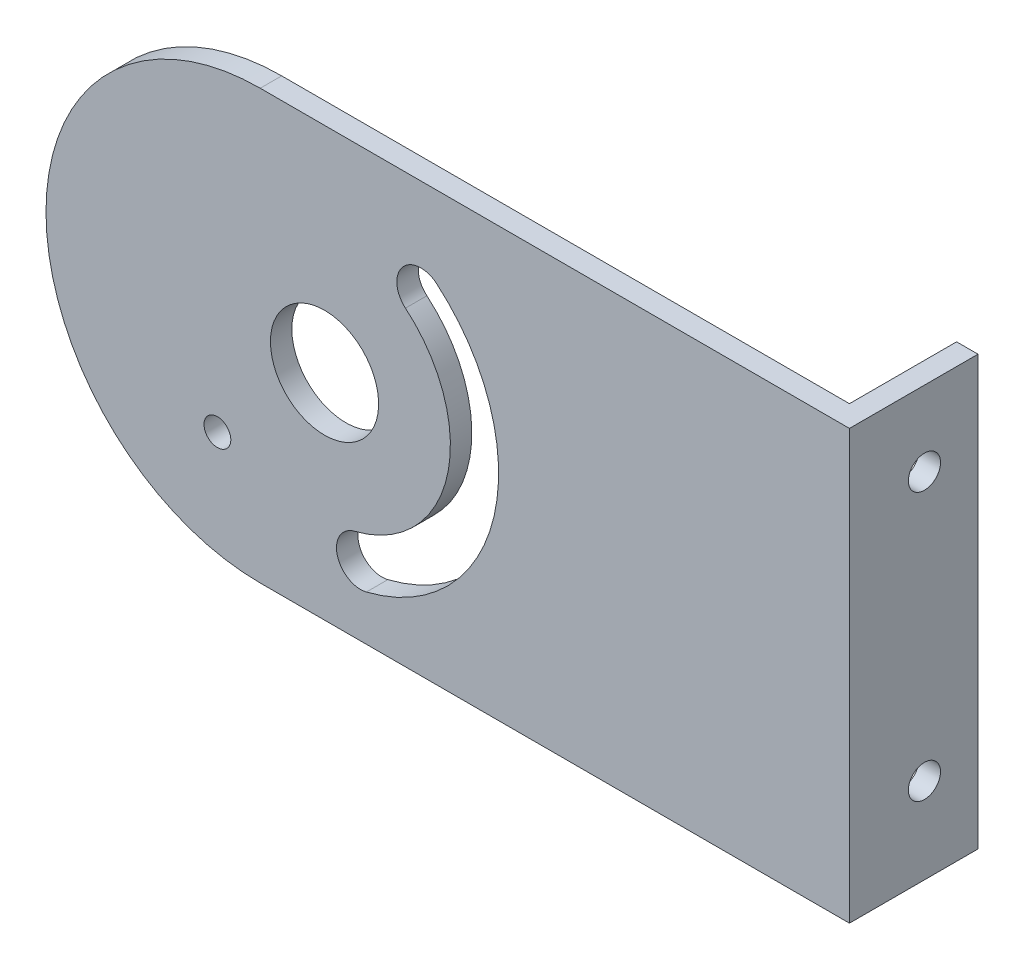
SolidWorks part; units mm, degrees
ref_plane "前视基准面" through (0, 0, 0) normal (0, 0, 1) x (1, 0, 0)
ref_plane "上视基准面" through (0, 0, 0) normal (0, 1, 0) x (1, 0, 0)
ref_plane "右视基准面" through (0, 0, 0) normal (1, 0, 0) x (0, 0, -1)
other "Configuration Table"
sketch "草图2" plane through (0, 0, 0) normal (0, 0, 1) x (1, 0, 0)
  line L0 (0, 0) -> (0, 40)
  line L1 (0, 40) -> (75, 40)
  line L2 (75, 40) -> (75, 0)
  line L3 (75, 0) -> (0, 0)
  dimension "D1" = 40
  dimension "D2" = 75
extrude "凸台-拉伸1" add sketch "草图2" along normal blind 2
sketch "草图3" plane through (0, 0, 0) normal (0, 0, -1) x (-1, 0, 0)
  line L0 (0, 40) -> (0, 0) construction
  line L6 (-75, 40) -> (0, 40) construction
  line L7 (-26, 20) -> (-35, 30.7238) construction
  line L8 (-26, 20) -> (-20.0822, 7.3122) construction
  circle A0 centre (-26, 20) radius 5.05
  circle A1 centre (-26, 20) radius 14 construction
  arc A3 (-35, 30.7238) -> (-29.3669, 6.4109) centre (-26, 20) ccw construction
  arc A4 (-36.4464, 32.4473) -> (-29.908, 4.2269) centre (-26, 20) ccw
  arc A5 (-33.5536, 29.0003) -> (-28.8258, 8.5949) centre (-26, 20) ccw
  arc A6 (-33.5536, 29.0003) -> (-36.4464, 32.4473) centre (-35, 30.7238) ccw
  arc A7 (-29.908, 4.2269) -> (-28.8258, 8.5949) centre (-29.3669, 6.4109) ccw
  circle A8 centre (-16, 10.202) radius 1.25
  point P13 (-39.6387, 16.84)
  dimension "D1" = 10.1
  dimension "D4" = 28
  dimension "D5" = 20
  dimension "D8" = 4.5
  dimension "D9" = 2.5
  dimension "D3" = 13.5891
  dimension "D2" = 26
  dimension "D6" = 165
  dimension "D7" = 9
  dimension "D10" = 10
extrude "切除-拉伸1" cut sketch "草图3" against normal through all
fillet "圆角1" radius 20 2 edges at (0, 40, 1) (0, 0, 1)
sketch "草图7" plane through (0, 0, 0) normal (0, 0, -1) x (-1, 0, 0)
  line L0 (-75, 40) -> (-20, 40) construction
  line L1 (-75, 0) -> (-73, 0)
  line L2 (-75, 0) -> (-75, 40)
  line L3 (-75, 40) -> (-73, 40)
  line L4 (-73, 0) -> (-73, 40)
  dimension "D1" = 2
extrude "凸台-拉伸3" add sketch "草图7" along normal blind 10
sketch "草图10" plane through (73, 0, 0) normal (-1, 0, 0) x (0, 0, 1)
  line L1 (0, 0) -> (0, 40) construction
  line L2 (-10, 40) -> (0, 40) construction
  circle A0 centre (-5, 33) radius 1.5
  circle A1 centre (-5, 8) radius 1.5
  dimension "D1" = 3
  dimension "D2" = 5
  dimension "D3" = 7
  dimension "D4" = 25
extrude "切除-拉伸4" cut sketch "草图10" against normal through all
